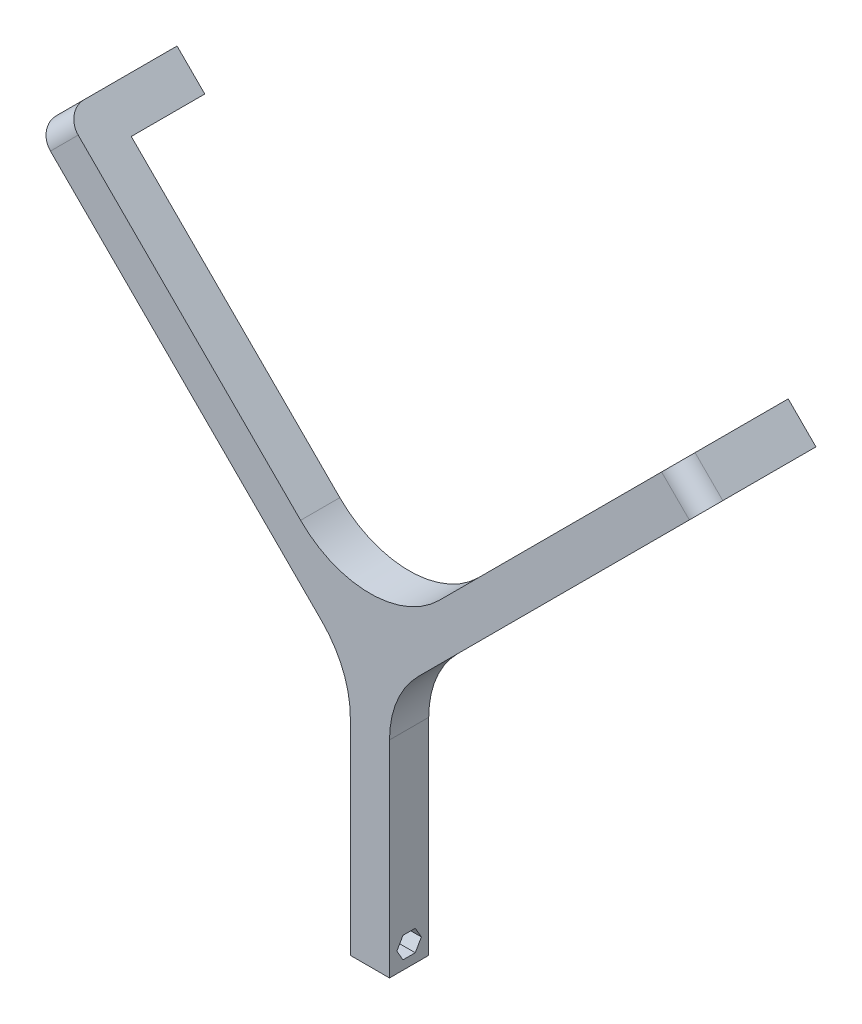
SolidWorks part; units mm, degrees
ref_plane "Plan de face" through (0, 0, 0) normal (0, 0, 1) x (1, 0, 0)
ref_plane "Plan de dessus" through (0, 0, 0) normal (0, 1, 0) x (1, 0, 0)
ref_plane "Plan de droite" through (0, 0, 0) normal (1, 0, 0) x (0, 0, -1)
sketch "Esquisse1" plane through (0, 0, 0) normal (0, 0, 1) x (1, 0, 0)
  line L1 (0, 0) -> (136, 0) construction
  line L2 (0, 0) -> (0, 120) construction
  line L3 (0, 120) -> (136, 120) construction
  line L4 (136, 0) -> (136, 120) construction
  line L16 (64, 0) -> (64, 50.3431)
  line L17 (64, 50.3431) -> (0, 114.3431)
  line L18 (0, 114.3431) -> (5.6569, 120)
  line L19 (5.6569, 120) -> (68, 57.6569)
  line L20 (68, 57.6569) -> (130.3431, 120)
  line L21 (130.3431, 120) -> (136, 114.3431)
  line L22 (136, 114.3431) -> (72, 50.3431)
  line L23 (72, 50.3431) -> (72, 0)
  line L24 (72, 0) -> (64, 0)
  point P7 (76.8777, 59.6544)
  point P15 (0, 99.6185)
  point P16 (57.298, 49.9986)
  point P17 (94.8481, 52.4126)
  point P18 (95.3846, 43.5615)
  point P19 (68, 0)
  point P20 (64, 38.4654)
  point P21 (72, 38.4654)
  point P22 (67.4902, 67.7008)
  point P23 (64, 35.2468)
  point P24 (66.4173, 68.7737)
  point P25 (66.4173, 60.9955)
  point P26 (67.6973, 57.6506)
  dimension "D1" = 136
  dimension "D2" = 120
  dimension "D3" = 8
  dimension "D4" = 68
  dimension "D5" = 135
  dimension "D6" = 135
  dimension "D7" = 90
  dimension "D8" = 8
  dimension "D9" = 8
  dimension "D10" = 68
extrude "Boss.-Extru.1" add sketch "Esquisse1" along normal blind 8
sketch "Esquisse2" plane through (0, 0, 0) normal (0, 0, -1) x (-1, 0, 0)
  line L0 (-72, 50.3431) -> (-136, 114.3431) construction
  line L1 (-136, 114.3431) -> (-130.3431, 120) construction
  line L2 (-130.3431, 120) -> (-68, 57.6569) construction
  line L3 (-130.3431, 108.6863) -> (-136, 114.3431)
  line L4 (-136, 114.3431) -> (-130.3431, 120)
  line L5 (-130.3431, 120) -> (-124.6863, 114.3431)
  line L6 (-130.3431, 108.6863) -> (-124.6863, 114.3431)
  line L7 (0, 114.3431) -> (-64, 50.3431) construction
  line L8 (-68, 57.6569) -> (-5.6569, 120) construction
  line L9 (-5.6569, 120) -> (0, 114.3431) construction
  line L10 (0, 114.3431) -> (-5.6569, 108.6863)
  line L11 (-11.3137, 114.3431) -> (-5.6569, 120)
  line L12 (-5.6569, 120) -> (0, 114.3431)
  line L13 (-11.3137, 114.3431) -> (-5.6569, 108.6863)
  dimension "D1" = 8
  dimension "D2" = 8
extrude "Boss.-Extru.2" add sketch "Esquisse2" along normal blind 15
fillet "Congé1" radius 20 3 edges at (72, 50.3431, 4) (64, 50.3431, 4) (68, 57.6569, 4)
fillet "Congé2" radius 4 2 edges at (133.1716, 117.1716, 8) (2.8284, 117.1716, 8)
sketch "Esquisse3" plane through (72, 0, 0) normal (1, 0, 0) x (0, 0, -1)
  line L0 (-8, 0) -> (-8, 42.0589) construction
  line L1 (-8, 0) -> (0, 0) construction
  line L3 (-2.75, 1.8349) -> (-1.5, 4)
  line L4 (-1.5, 4) -> (-2.75, 6.1651)
  line L5 (-2.75, 6.1651) -> (-5.25, 6.1651)
  line L6 (-5.25, 6.1651) -> (-6.5, 4)
  line L7 (-6.5, 4) -> (-5.25, 1.8349)
  line L8 (-5.25, 1.8349) -> (-2.75, 1.8349)
  circle A0 centre (-4, 4) radius 2.5 construction
  circle A1 centre (-4, 4) radius 2.5 construction
  dimension "D3" = 5
  dimension "D4" = 5
  dimension "D1" = 4
  dimension "D2" = 4
extrude "Enlèv. mat.-Extru.1" cut sketch "Esquisse3" against normal up to surface (8 mm away) up to face at (64, 21.0294, 4)
equation "\"long_tot\"= 120"
equation "\"espac_sub_arms\"= 120"
equation "\"épaiss_cadre\"= 8"
equation "\"long_protub\"= 15"
equation "\"rayon_conge\"= 3"
equation "\"diam_axe\"= 5"
equation "\"D1@Esquisse1\"=\"espac_sub_arms\"+\"épaiss_cadre\"*2"
equation "\"D2@Esquisse1\"=\"long_tot\""
equation "\"D3@Esquisse1\"=\"épaiss_cadre\""
equation "\"D4@Esquisse1\"=\"D1@Esquisse1\"/2"
equation "\"D6@Esquisse1\"=\"D5@Esquisse1\""
equation "\"D8@Esquisse1\"=\"épaiss_cadre\""
equation "\"D9@Esquisse1\"=\"épaiss_cadre\""
equation "\"D10@Esquisse1\"=\"D4@Esquisse1\""
equation "\"D1@Boss.-Extru.1\"=\"épaiss_cadre\""
equation "\"D1@Esquisse2\"=\"épaiss_cadre\""
equation "\"D2@Esquisse2\"=\"épaiss_cadre\""
equation "\"D1@Boss.-Extru.2\"=\"long_protub\""
equation "\"D1@Esquisse3\"=\"épaiss_cadre\"/2"
equation "\"D2@Esquisse3\"=\"épaiss_cadre\"/2"
